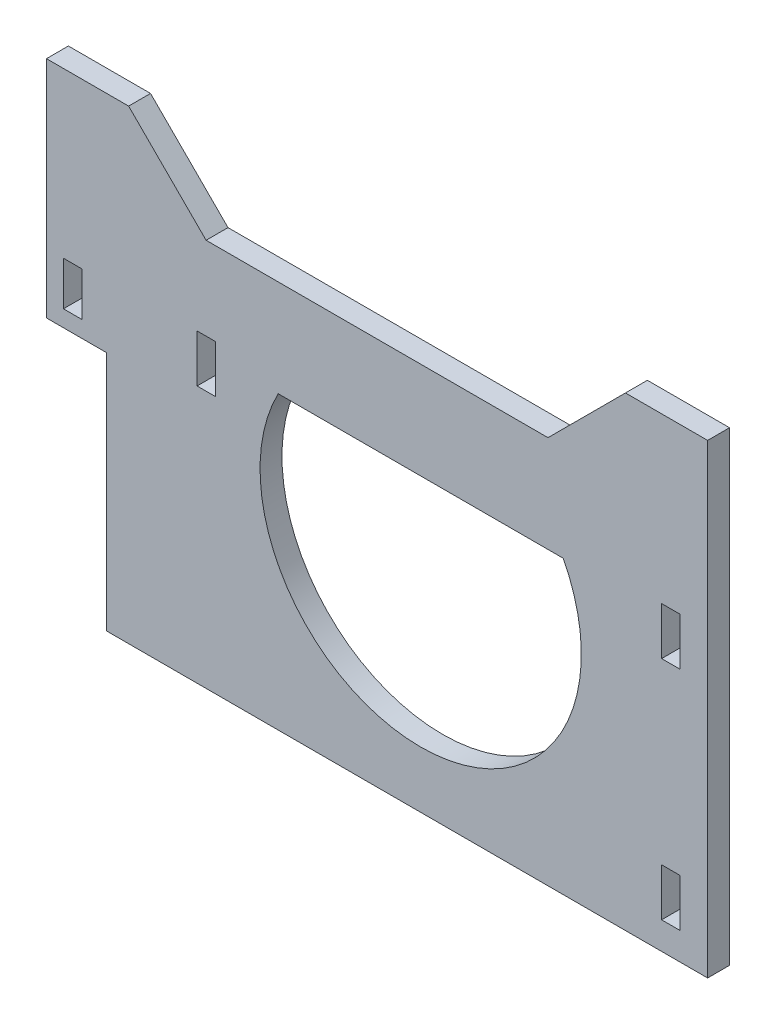
SolidWorks part; units mm, degrees
ref_plane "Front Plane" through (0, 0, 0) normal (0, 0, 1) x (1, 0, 0)
ref_plane "Top Plane" through (0, 0, 0) normal (0, 1, 0) x (1, 0, 0)
ref_plane "Right Plane" through (0, 0, 0) normal (1, 0, 0) x (0, 0, -1)
sketch "Sketch1" plane through (0, 0, 0) normal (0, 0, 1) x (1, 0, 0)
  line L0 (-25.9, 23.1791) -> (26.1356, 23.1791)
  line L6 (-40.7, 25.7) -> (-37.3, 25.7)
  line L9 (-40.7, 25.7) -> (-40.7, 17)
  line L12 (-40.7, 17) -> (-37.3, 17)
  line L15 (-37.3, 25.7) -> (-37.3, 17)
  line L51 (52.5, 30) -> (52.5, -30)
  line L54 (44.1, 25) -> (47.5, 25)
  line L55 (44.1, 25) -> (44.1, 16.3)
  line L56 (44.1, 16.3) -> (47.5, 16.3)
  line L57 (47.5, 25) -> (47.5, 16.3)
  line L58 (47.5, -16.3) -> (44.1, -16.3)
  line L59 (47.5, -16.3) -> (47.5, -25)
  line L60 (47.5, -25) -> (44.1, -25)
  line L61 (44.1, -16.3) -> (44.1, -25)
  line L65 (-65.1, 25) -> (-61.7, 25)
  line L66 (-65.1, 25) -> (-65.1, 17)
  line L67 (-65.1, 17) -> (-61.7, 17)
  line L68 (-61.7, 25) -> (-61.7, 17)
  line L76 (52.5, 30) -> (-68.2, 30)
  line L81 (-39, 25.7) -> (-39, 17) construction
  line L82 (-37.3, 21.35) -> (-40.7, 21.35) construction
  line L83 (-63.4, 25) -> (-63.4, 17) construction
  line L84 (-61.7, 21) -> (-65.1, 21) construction
  line L85 (47.5, 20.65) -> (44.1, 20.65) construction
  line L86 (45.8, 25) -> (45.8, 16.3) construction
  line L87 (45.8, -16.3) -> (45.8, -25) construction
  line L88 (47.5, -20.65) -> (44.1, -20.65) construction
  line L89 (-57.2, -30) -> (-57.2, 14)
  line L90 (-57.2, 14) -> (-68.2, 14)
  line L91 (-68.2, 14) -> (-68.2, 30)
  line L92 (-57.2, -30) -> (52.5, -30)
  arc A12 (-25.9, 23.1791) -> (26.1356, 23.1791) centre (0.1178, 9.6488) ccw
  point P0 (0, 0)
  point P5 (-32.1081, 25)
  point P14 (52.5, 0)
  point P25 (-7.85, 30)
  point P26 (26.0356, 23.74)
  point P34 (-25.9, 23.1791)
  dimension "D3" = 3.4
  dimension "D4" = 8.7
  dimension "D6" = 60
  dimension "D5" = 24.4
  dimension "D7" = 53.65
  dimension "D2" = 31.15
  dimension "D10" = 20.65
  dimension "D11" = 20.65
  dimension "D8" = 120.7
  dimension "D9" = 11
  dimension "D12" = 44
extrude "Boss-Extrude1" add sketch "Sketch1" along normal blind 4
sketch "Sketch2" plane through (0, 0, 0) normal (0, 0, 1) x (1, 0, 0)
  line L0 (-68.2, 30) -> (52.5, 30)
  line L4 (23.3579, 40.8579) -> (-39.0579, 40.8579)
  line L5 (-39.0579, 40.8579) -> (-53.2, 55)
  line L6 (-53.2, 55) -> (-68.2, 55)
  line L7 (-68.2, 55) -> (-68.2, 30)
  line L8 (23.3579, 40.8579) -> (37.5, 55)
  line L9 (37.5, 55) -> (52.5, 55)
  line L10 (52.5, 55) -> (52.5, 30)
  line L12 (-68.2, 30) -> (-68.2, 14) construction
  dimension "D1" = 25
  dimension "D2" = 20
  dimension "D3" = 15
  dimension "D4" = 135
extrude "Boss-Extrude2" add sketch "Sketch2" along normal blind 4
sketch "Sketch3" plane through (0, 0, 0) normal (0, 0, -1) x (-1, 0, 0)
  line L0 (-45.8, 25) -> (-45.8, 16.3) construction
  line L1 (-47.5, 25) -> (-44.1, 25) construction
  line L2 (-44.1, 16.3) -> (-47.5, 16.3) construction
  line L3 (-47.5, 20.65) -> (-44.1, 20.65) construction
  line L4 (-47.5, 16.3) -> (-47.5, 25) construction
  line L5 (-44.1, 25) -> (-44.1, 16.3) construction
  line L6 (-45.8, -16.3) -> (-45.8, -25) construction
  line L7 (-47.5, -16.3) -> (-44.1, -16.3) construction
  line L8 (-44.1, -25) -> (-47.5, -25) construction
  line L9 (-47.5, -20.65) -> (-44.1, -20.65) construction
  line L10 (-47.5, -25) -> (-47.5, -16.3) construction
  line L11 (-44.1, -16.3) -> (-44.1, -25) construction
  line L12 (39, 25.7) -> (39, 17) construction
  line L13 (37.3, 25.7) -> (40.7, 25.7) construction
  line L14 (40.7, 17) -> (37.3, 17) construction
  line L15 (37.3, 21.35) -> (40.7, 21.35) construction
  line L16 (37.3, 17) -> (37.3, 25.7) construction
  line L17 (40.7, 25.7) -> (40.7, 17) construction
  line L18 (63.4, 25) -> (63.4, 17) construction
  line L19 (61.7, 25) -> (65.1, 25) construction
  line L20 (65.1, 17) -> (61.7, 17) construction
  line L21 (61.7, 21) -> (65.1, 21) construction
  line L22 (61.7, 17) -> (61.7, 25) construction
  line L23 (65.1, 25) -> (65.1, 17) construction
equation "\"pin_hole_width\"=3.4"
equation "\"D3@Sketch1\"=\"pin_hole_width\""
equation "\"pin_hole_height\"=8.7"
equation "\"D4@Sketch1\"=\"pin_hole_height\""
